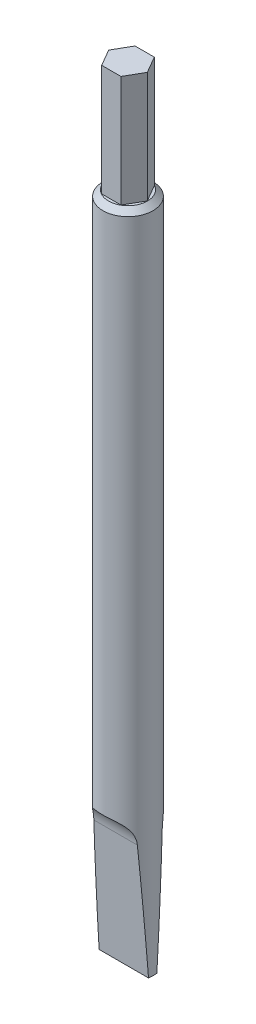
SolidWorks part; units mm, degrees
material "Cast Alloy Steel"
ref_plane "Front Plane" through (0, 0, 0) normal (0, 0, 1) x (1, 0, 0)
ref_plane "Top Plane" through (0, 0, 0) normal (0, 1, 0) x (1, 0, 0)
ref_plane "Right Plane" through (0, 0, 0) normal (1, 0, 0) x (0, 0, -1)
sketch "Sketch2" plane through (0, 0, 0) normal (0, 1, 0) x (1, 0, 0)
  line L0 (-1.7321, 3) -> (1.7321, 3)
  line L1 (1.7321, 3) -> (3.4641, 0)
  line L2 (3.4641, 0) -> (1.7321, -3)
  line L3 (1.7321, -3) -> (-1.7321, -3)
  line L4 (-1.7321, -3) -> (-3.4641, 0)
  line L5 (-3.4641, 0) -> (-1.7321, 3)
  circle A0 centre (0, 0) radius 3.4641 construction
  circle A1 centre (0, 0) radius 4.5
  dimension "D1" = 6
  dimension "D2" = 9
extrude "Boss-Extrude1" add sketch "Sketch2" along normal blind 20 contours L5 L4 L3 L2 L1 L0 region at (0, 0, 0)
extrude "Boss-Extrude2" add sketch "Sketch2<3>" against normal blind 120 contours L5 L4 L3 L2 L1 L0 | A1 L4 L5 L0 L1 L2 L3 region at (0, 0, 0) region at (-4.3727, 0, 0)
sketch "Sketch2<3>" plane through (0, 0, 0) normal (0, 1, 0) x (1, 0, 0) same geometry as "Sketch2"
chamfer "Chamfer1" distance 1 angle 45 1 edges at (0, 0, 4.5)
sketch "Sketch3" plane through (0, 0, 0) normal (1, 0, 0) x (0, 0, -1)
  line L0 (0, -120) -> (0, -87.7685) construction
  line L1 (-4.5, -120) -> (4.5, -120) construction
  line L2 (4.5, -95) -> (4.5, -120)
  line L3 (4.5, -120) -> (4.5, -1) construction
  line L4 (4.5, -120) -> (0.75, -120)
  line L5 (0.75, -120) -> (2.229, -98.8487)
  line L6 (-0.75, -120) -> (-2.229, -98.8487)
  line L7 (-4.5, -120) -> (-0.75, -120)
  line L8 (-4.5, -95) -> (-4.5, -120)
  arc A0 (2.229, -98.8487) -> (4.5, -95) centre (7.2169, -99.1975) cw
  arc A1 (-2.229, -98.8487) -> (-4.5, -95) centre (-7.2169, -99.1975) ccw
  dimension "D1" = 5
  dimension "D2" = 4
  dimension "D3" = 1.5
  dimension "D4" = 25
extrude "Cut-Extrude1" cut sketch "Sketch3" against normal through all both and the other way through all
